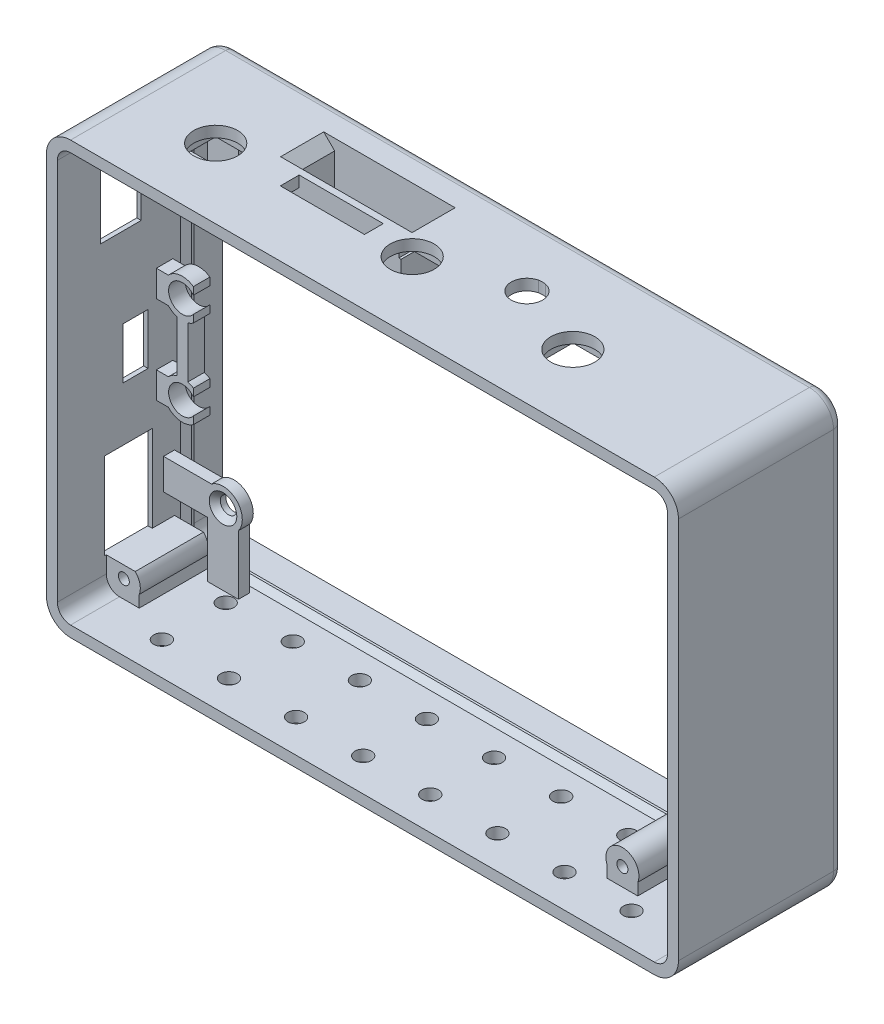
SolidWorks part; units mm, degrees
ref_plane "Спереди" through (0, 0, 0) normal (0, 0, 1) x (1, 0, 0)
ref_plane "Сверху" through (0, 0, 0) normal (0, 1, 0) x (1, 0, 0)
ref_plane "Справа" through (0, 0, 0) normal (1, 0, 0) x (0, 0, -1)
sketch "основной шаблон" plane through (0, 0, 0) normal (0, 0, 1) x (1, 0, 0)
  line L0 (57.46, -33.28) -> (57.46, 36.28)
  line L1 (53.06, 40.68) -> (-53.06, 40.68)
  line L2 (55.46, -33.28) -> (55.46, 36.28)
  line L3 (53.06, 38.68) -> (-53.06, 38.68)
  line L4 (53.357, 32.7) -> (55.46, 32.7)
  line L5 (49.48, 36.577) -> (49.48, 38.68)
  line L6 (35.5675, 36.5758) -> (35.5675, 38.68)
  line L7 (41.1675, 36.5758) -> (41.1675, 38.68)
  line L8 (-8.24, 37.68) -> (53.06, 37.68)
  line L9 (54.46, 36.28) -> (54.46, -33.28)
  line L10 (51.56, 22.97) -> (55.46, 22.97)
  line L11 (52.26, 28.57) -> (55.46, 28.57)
  line L12 (52.26, 28.57) -> (52.26, 32.5001)
  line L13 (46.66, 27.87) -> (46.66, 38.68)
  line L14 (-53.06, -35.68) -> (53.06, -35.68)
  line L15 (-53.06, -37.68) -> (53.06, -37.68)
  line L16 (41.1675, -33.5233) -> (41.1675, -35.68)
  line L17 (35.5675, -33.5233) -> (35.5675, -35.68)
  line L18 (49.48, -33.577) -> (49.48, -35.68)
  line L19 (53.357, -29.7) -> (55.46, -29.7)
  line L20 (53.06, -34.68) -> (-53.06, -34.68)
  line L21 (51.56, -19.97) -> (55.46, -19.97)
  line L22 (52.26, -25.57) -> (55.46, -25.57)
  line L23 (52.26, -25.57) -> (52.26, -29.5001)
  line L24 (46.66, -24.87) -> (46.66, -35.68)
  line L25 (50.06, -40.68) -> (46.06, -40.68)
  line L26 (46.06, -37.68) -> (46.06, -40.68)
  line L27 (50.06, -40.68) -> (50.06, -37.68)
  line L28 (-46.06, -40.68) -> (-50.06, -40.68)
  line L29 (-50.06, -37.68) -> (-50.06, -40.68)
  line L30 (-46.06, -40.68) -> (-46.06, -37.68)
  line L31 (-55.46, 36.28) -> (-55.46, -33.28)
  line L32 (-57.46, 36.28) -> (-57.46, -33.28)
  line L33 (-47.44, -25.57) -> (-47.44, -35.68)
  line L34 (-47.44, -25.57) -> (-55.46, -25.57)
  line L35 (-46.74, -19.97) -> (-55.46, -19.97)
  line L36 (-41.84, -24.87) -> (-41.84, -35.68)
  line L37 (-53.3558, -29.6462) -> (-55.46, -29.6462)
  line L38 (-55.46, -30.6537) -> (-49.8732, -30.6537)
  line L39 (-49.4788, -33.5233) -> (-49.4788, -35.68)
  line L40 (-54.46, -33.28) -> (-54.46, 36.28)
  line L41 (-53.2825, -5.7) -> (-55.3212, -5.7)
  line L42 (-48.735, -5.2277) -> (-48.735, -6.6)
  line L43 (-48.735, -9.6) -> (-48.735, -10.9723)
  line L44 (-55.46, -10.5) -> (-53.2825, -10.5)
  line L45 (-49.735, -4.7459) -> (-49.735, 4.5459)
  line L46 (-51.735, 4.5459) -> (-51.735, -4.7459)
  line L47 (-55.46, 5.5) -> (-53.2825, 5.5)
  line L48 (-53.2825, 10.3) -> (-55.46, 10.3)
  line L49 (-48.735, 10.7723) -> (-48.735, 9.4)
  line L50 (-48.735, 6.4) -> (-48.735, 5.0277)
  line L51 (-55.46, -30.28) -> (-56.66, -30.28)
  line L52 (-56.66, -31.8537) -> (-56.66, -13.3537)
  line L53 (-55.46, -14.5537) -> (-56.66, -14.5537)
  line L54 (-55.46, 4.5685) -> (-56.66, 4.5685)
  line L55 (-56.66, -5.9315) -> (-56.66, 5.7685)
  line L56 (-55.46, -4.7315) -> (-56.66, -4.7315)
  line L57 (-56.66, 12.5883) -> (-56.66, 33.9619)
  line L58 (-55.46, 13.7883) -> (-56.66, 13.7883)
  line L59 (-55.46, 32.7619) -> (-56.66, 32.7619)
  line L60 (-41.84, 27.87) -> (-41.84, 38.68)
  line L61 (-47.44, 28.57) -> (-47.44, 38.68)
  line L62 (-47.44, 28.57) -> (-55.46, 28.57)
  line L63 (-46.74, 22.97) -> (-55.46, 22.97)
  line L64 (-49.4785, 38.68) -> (-53.06, 38.68)
  line L65 (-53.06, 37.68) -> (-30.54, 37.68)
  line L66 (-49.4785, 36.576) -> (-49.4785, 38.68)
  line L67 (-51.0505, 32.7619) -> (-55.46, 32.7619)
  line L68 (8.897, 38.68) -> (15.497, 38.68)
  line L69 (15.497, 40.68) -> (8.897, 40.68)
  line L70 (-30.54, 29.68) -> (-30.54, 38.68)
  line L71 (-8.24, 29.68) -> (-30.54, 29.68)
  line L72 (-8.24, 29.68) -> (-8.24, 38.68)
  line L73 (-11.24, 30.88) -> (-11.24, 30.08)
  line L74 (-9.44, 30.08) -> (-9.44, 40.68)
  line L75 (-10.4737, 38.68) -> (-10.4737, 40.68)
  line L76 (-27.54, 29.68) -> (-27.54, 30.08)
  line L77 (-27.54, 30.88) -> (-27.54, 30.08)
  line L78 (-29.34, 30.08) -> (-29.34, 40.68)
  line L79 (-26.7737, 38.68) -> (-26.7737, 40.68)
  line L80 (-11.24, 29.68) -> (-11.24, 30.08)
  arc A0 (57.46, 36.28) -> (53.06, 40.68) centre (53.06, 36.28) ccw
  arc A1 (55.46, 36.28) -> (53.06, 38.68) centre (53.06, 36.28) ccw
  arc A2 (49.48, 36.577) -> (53.357, 32.7) centre (52.28, 35.5) ccw
  circle A3 centre (52.28, 35.5) radius 1
  circle A4 centre (38.3675, 35.4988) radius 1
  arc A5 (35.5675, 36.5758) -> (41.1675, 36.5758) centre (38.3675, 35.4988) ccw
  circle A6 centre (49.46, 25.77) radius 1.5
  arc A7 (46.66, 27.87) -> (51.56, 22.97) centre (49.46, 25.77) ccw
  arc A8 (54.46, 36.28) -> (53.06, 37.68) centre (53.06, 36.28) ccw
  arc A9 (53.06, -37.68) -> (57.46, -33.28) centre (53.06, -33.28) ccw
  arc A10 (53.06, -35.68) -> (55.46, -33.28) centre (53.06, -33.28) ccw
  circle A11 centre (38.3675, -32.4462) radius 1
  arc A12 (41.1675, -33.5233) -> (35.5675, -33.5233) centre (38.3675, -32.4462) ccw
  circle A13 centre (52.28, -32.5) radius 1
  arc A14 (53.357, -29.7) -> (49.48, -33.577) centre (52.28, -32.5) ccw
  circle A15 centre (49.46, -22.77) radius 1.5
  circle A16 centre (49.46, -22.77) radius 3.5
  arc A17 (53.06, -34.68) -> (54.46, -33.28) centre (53.06, -33.28) ccw
  arc A18 (-55.46, -33.28) -> (-53.06, -35.68) centre (-53.06, -33.28) ccw
  arc A19 (-57.46, -33.28) -> (-53.06, -37.68) centre (-53.06, -33.28) ccw
  circle A20 centre (-44.64, -22.77) radius 1.5
  circle A21 centre (-44.64, -22.77) radius 3.5
  arc A22 (-49.8732, -30.6537) -> (-53.3558, -29.6462) centre (-52.2788, -32.4462) ccw
  circle A23 centre (-52.2788, -32.4462) radius 1
  arc A24 (-49.4788, -33.5233) -> (-49.8732, -30.6537) centre (-52.2788, -32.4462) ccw
  arc A25 (-48.735, -5.2277) -> (-49.735, -4.7459) centre (-50.735, -8.1) ccw
  arc A26 (-51.735, -4.7459) -> (-53.2825, -5.7) centre (-50.735, -8.1) ccw
  arc A27 (-48.735, -6.6) -> (-48.735, -9.6) centre (-50.735, -8.1) ccw
  arc A28 (-53.2825, -10.5) -> (-48.735, -10.9723) centre (-50.735, -8.1) ccw
  arc A29 (-48.735, 9.4) -> (-48.735, 6.4) centre (-50.735, 7.9) ccw
  arc A30 (-49.735, 4.5459) -> (-48.735, 5.0277) centre (-50.735, 7.9) ccw
  arc A31 (-53.2825, 5.5) -> (-51.735, 4.5459) centre (-50.735, 7.9) ccw
  arc A32 (-48.735, 10.7723) -> (-53.2825, 10.3) centre (-50.735, 7.9) ccw
  arc A33 (-54.46, -33.28) -> (-53.06, -34.68) centre (-53.06, -33.28) ccw
  arc A34 (-56.66, -31.8537) -> (-57.46, -32.9851) centre (-56.26, -32.9851) ccw
  arc A35 (-57.46, -12.2223) -> (-56.66, -13.3537) centre (-56.26, -12.2223) ccw
  arc A36 (-57.46, 6.8999) -> (-56.66, 5.7685) centre (-56.26, 6.8999) ccw
  arc A37 (-56.66, -5.9315) -> (-57.46, -7.0629) centre (-56.26, -7.0629) ccw
  arc A38 (-56.66, 12.5883) -> (-57.46, 11.4569) centre (-56.26, 11.4569) ccw
  arc A39 (-57.46, 35.0932) -> (-56.66, 33.9619) centre (-56.26, 35.0932) ccw
  arc A40 (-53.06, 37.68) -> (-54.46, 36.28) centre (-53.06, 36.28) ccw
  arc A41 (-53.06, 40.68) -> (-57.46, 36.28) centre (-53.06, 36.28) ccw
  arc A42 (-53.06, 38.68) -> (-55.46, 36.28) centre (-53.06, 36.28) ccw
  circle A43 centre (-44.64, 25.77) radius 1.5
  circle A44 centre (-44.64, 25.77) radius 3.5
  circle A45 centre (-52.2785, 35.499) radius 1
  arc A46 (-53.3555, 32.699) -> (-51.0505, 32.7619) centre (-52.2785, 35.499) ccw
  arc A47 (-51.0505, 32.7619) -> (-49.4785, 36.576) centre (-52.2785, 35.499) ccw
sketch "Эскиз2" plane through (0, 0, 0) normal (0, 0, 1) x (1, 0, 0)
  line L0 (-55.46, 36.28) -> (-55.46, -33.28) construction
  line L1 (53.06, 38.68) -> (-53.06, 38.68) construction
  line L2 (-57.46, 36.28) -> (-57.46, -33.28) construction
  line L3 (53.06, 40.68) -> (-53.06, 40.68) construction
  line L4 (-55.46, 36.28) -> (-55.46, -33.28)
  line L5 (53.06, 38.68) -> (-53.06, 38.68)
  line L6 (-57.46, 36.28) -> (-57.46, -33.28)
  line L7 (53.06, 40.68) -> (-53.06, 40.68)
  line L8 (55.46, -33.28) -> (55.46, 36.28) construction
  line L9 (57.46, -33.28) -> (57.46, 36.28) construction
  line L10 (55.46, -33.28) -> (55.46, 36.28)
  line L11 (57.46, -33.28) -> (57.46, 36.28)
  line L12 (-53.06, -37.68) -> (53.06, -37.68) construction
  line L13 (-53.06, -35.68) -> (53.06, -35.68) construction
  line L14 (-53.06, -37.68) -> (53.06, -37.68)
  line L15 (-53.06, -35.68) -> (53.06, -35.68)
  arc A0 (-53.06, 38.68) -> (-55.46, 36.28) centre (-53.06, 36.28) ccw construction
  arc A1 (-53.06, 40.68) -> (-57.46, 36.28) centre (-53.06, 36.28) ccw construction
  arc A2 (-53.06, 38.68) -> (-55.46, 36.28) centre (-53.06, 36.28) ccw
  arc A3 (-53.06, 40.68) -> (-57.46, 36.28) centre (-53.06, 36.28) ccw
  arc A4 (57.46, 36.28) -> (53.06, 40.68) centre (53.06, 36.28) ccw construction
  arc A5 (55.46, 36.28) -> (53.06, 38.68) centre (53.06, 36.28) ccw construction
  arc A6 (57.46, 36.28) -> (53.06, 40.68) centre (53.06, 36.28) ccw
  arc A7 (55.46, 36.28) -> (53.06, 38.68) centre (53.06, 36.28) ccw
  arc A8 (53.06, -37.68) -> (57.46, -33.28) centre (53.06, -33.28) ccw construction
  arc A9 (53.06, -35.68) -> (55.46, -33.28) centre (53.06, -33.28) ccw construction
  arc A10 (53.06, -37.68) -> (57.46, -33.28) centre (53.06, -33.28) ccw
  arc A11 (53.06, -35.68) -> (55.46, -33.28) centre (53.06, -33.28) ccw
  arc A12 (-57.46, -33.28) -> (-53.06, -37.68) centre (-53.06, -33.28) ccw construction
  arc A13 (-55.46, -33.28) -> (-53.06, -35.68) centre (-53.06, -33.28) ccw construction
  arc A14 (-57.46, -33.28) -> (-53.06, -37.68) centre (-53.06, -33.28) ccw
  arc A15 (-55.46, -33.28) -> (-53.06, -35.68) centre (-53.06, -33.28) ccw
extrude "рамка" add sketch "Эскиз2" along normal blind 30
ref_plane "Плоскость4" through (0, 0, 6.2) normal (0, 0, -1) x (-1, 0, 0)
sketch "Эскиз6" plane through (0, 0, 6.2) normal (0, 0, -1) x (-1, 0, 0)
  line L0 (-55.46, -33.28) -> (-55.46, 36.28) construction
  line L1 (-54.46, 36.28) -> (-54.46, -33.28) construction
  line L2 (-55.46, -33.28) -> (-55.46, 36.28)
  line L3 (-54.46, 36.28) -> (-54.46, -33.28)
  line L4 (8.24, 37.68) -> (-53.06, 37.68) construction
  line L5 (8.24, 37.68) -> (-53.06, 37.68)
  line L6 (53.06, -35.68) -> (-53.06, -35.68) construction
  line L7 (-53.06, -34.68) -> (53.06, -34.68) construction
  line L8 (53.06, -35.68) -> (-53.06, -35.68)
  line L9 (-53.06, -34.68) -> (53.06, -34.68)
  line L10 (54.46, -33.28) -> (54.46, 36.28) construction
  line L11 (55.46, 36.28) -> (55.46, -33.28) construction
  line L12 (54.46, -33.28) -> (54.46, 36.28)
  line L13 (55.46, 36.28) -> (55.46, -33.28)
  line L14 (53.06, 37.68) -> (30.54, 37.68) construction
  line L15 (53.06, 37.68) -> (30.54, 37.68)
  line L16 (30.54, 37.68) -> (30.54, 38.68)
  line L17 (30.54, 38.68) -> (53.06, 38.68)
  line L18 (8.24, 37.68) -> (8.24, 38.68)
  line L19 (8.24, 38.68) -> (-53.06, 38.68)
  arc A0 (-53.06, 37.68) -> (-54.46, 36.28) centre (-53.06, 36.28) ccw construction
  arc A1 (-53.06, 38.68) -> (-55.46, 36.28) centre (-53.06, 36.28) ccw construction
  arc A2 (-53.06, 37.68) -> (-54.46, 36.28) centre (-53.06, 36.28) ccw
  arc A3 (-53.06, 38.68) -> (-55.46, 36.28) centre (-53.06, 36.28) ccw
  arc A4 (-55.46, -33.28) -> (-53.06, -35.68) centre (-53.06, -33.28) ccw construction
  arc A5 (-54.46, -33.28) -> (-53.06, -34.68) centre (-53.06, -33.28) ccw construction
  arc A6 (-55.46, -33.28) -> (-53.06, -35.68) centre (-53.06, -33.28) ccw
  arc A7 (-54.46, -33.28) -> (-53.06, -34.68) centre (-53.06, -33.28) ccw
  arc A8 (53.06, -34.68) -> (54.46, -33.28) centre (53.06, -33.28) ccw construction
  arc A9 (53.06, -35.68) -> (55.46, -33.28) centre (53.06, -33.28) ccw construction
  arc A10 (53.06, -34.68) -> (54.46, -33.28) centre (53.06, -33.28) ccw
  arc A11 (53.06, -35.68) -> (55.46, -33.28) centre (53.06, -33.28) ccw
  arc A12 (55.46, 36.28) -> (53.06, 38.68) centre (53.06, 36.28) ccw construction
  arc A13 (54.46, 36.28) -> (53.06, 37.68) centre (53.06, 36.28) ccw construction
  arc A14 (55.46, 36.28) -> (53.06, 38.68) centre (53.06, 36.28) ccw
  arc A15 (54.46, 36.28) -> (53.06, 37.68) centre (53.06, 36.28) ccw
extrude "юбка" add sketch "Эскиз6" against normal blind 2.4
chamfer "фаска юбки" distance 2 angle 45 9 edges at (-41.8, 37.68, 8.6) (-54.0499, 37.2699, 8.6) (-54.46, 1.5, 8.6) (-54.0499, -34.2699, 8.6) (0, -34.68, 8.6) (54.0499, -34.2699, 8.6) (54.46, 1.5, 8.6) (54.0499, 37.2699, 8.6) (22.41, 37.68, 8.6)
ref_plane "Плоскость5" through (0, 0, 8.7) normal (0, 0, -1) x (-1, 0, 0)
sketch "Эскиз7" plane through (0, 0, 8.7) normal (0, 0, -1) x (-1, 0, 0)
  line L0 (-35.5675, 36.5758) -> (-35.5675, 38.68) construction
  line L1 (-41.1675, 36.5758) -> (-41.1675, 38.68) construction
  line L2 (-35.5675, 36.5758) -> (-35.5675, 38.68)
  line L3 (-41.1675, 36.5758) -> (-41.1675, 38.68)
  line L4 (-41.1675, 38.68) -> (-35.5675, 38.68)
  line L5 (-49.48, 38.68) -> (-53.06, 38.68)
  line L6 (-53.357, 32.7) -> (-55.46, 32.7) construction
  line L7 (-52.26, 28.57) -> (-52.26, 32.5001) construction
  line L8 (-52.26, 28.57) -> (-55.46, 28.57) construction
  line L9 (-51.56, 22.97) -> (-55.46, 22.97) construction
  line L10 (-46.66, 27.87) -> (-46.66, 38.68) construction
  line L11 (-53.357, 32.7) -> (-55.46, 32.7)
  line L12 (-52.26, 28.57) -> (-52.26, 32.5001)
  line L13 (-52.26, 28.57) -> (-55.46, 28.57)
  line L14 (-51.56, 22.97) -> (-55.46, 22.97)
  line L15 (-46.66, 27.87) -> (-46.66, 38.68)
  line L16 (-46.66, 38.68) -> (-49.48, 38.68)
  line L17 (-55.46, 36.28) -> (-55.46, 32.7)
  line L18 (-55.46, 28.57) -> (-55.46, 22.97)
  line L19 (-41.1675, -33.5233) -> (-41.1675, -35.68) construction
  line L20 (-35.5675, -33.5233) -> (-35.5675, -35.68) construction
  line L21 (-41.1675, -33.5233) -> (-41.1675, -35.68)
  line L22 (-35.5675, -33.5233) -> (-35.5675, -35.68)
  line L23 (-52.26, -25.57) -> (-52.26, -29.5001) construction
  line L24 (-53.357, -29.7) -> (-55.46, -29.7) construction
  line L26 (-52.26, -25.57) -> (-55.46, -25.57) construction
  line L27 (-51.56, -19.97) -> (-55.46, -19.97) construction
  line L28 (-46.66, -24.87) -> (-46.66, -35.68) construction
  line L29 (-52.26, -25.57) -> (-52.26, -29.5001)
  line L30 (-53.357, -29.7) -> (-55.46, -29.7)
  line L32 (-52.26, -25.57) -> (-55.46, -25.57)
  line L33 (-51.56, -19.97) -> (-55.46, -19.97)
  line L34 (-46.66, -24.87) -> (-46.66, -35.68)
  line L35 (-55.46, -19.97) -> (-55.46, -25.57)
  line L37 (-55.46, -29.7) -> (-55.46, -33.28)
  line L38 (-53.06, -35.68) -> (-46.66, -35.68)
  line L39 (-35.5675, -35.68) -> (-41.1675, -35.68)
  line L40 (53.3558, -29.6462) -> (55.46, -29.6462) construction
  line L41 (49.4788, -33.5233) -> (49.4788, -35.68) construction
  line L42 (41.84, -24.87) -> (41.84, -35.68) construction
  line L43 (47.44, -25.57) -> (47.44, -35.68) construction
  line L44 (47.44, -25.57) -> (55.46, -25.57) construction
  line L45 (46.74, -19.97) -> (55.46, -19.97) construction
  line L46 (53.3558, -29.6462) -> (55.46, -29.6462)
  line L47 (49.4788, -33.5233) -> (49.4788, -35.68)
  line L48 (41.84, -24.87) -> (41.84, -35.68)
  line L49 (47.44, -25.57) -> (47.44, -35.68)
  line L50 (47.44, -25.57) -> (55.46, -25.57)
  line L51 (46.74, -19.97) -> (55.46, -19.97)
  line L52 (55.46, -19.97) -> (55.46, -25.57)
  line L53 (55.46, -29.6462) -> (55.46, -33.28)
  line L54 (53.06, -35.68) -> (49.4788, -35.68)
  line L55 (47.44, -35.68) -> (41.84, -35.68)
  line L56 (47.44, 28.57) -> (47.44, 38.68) construction
  line L57 (47.44, 28.57) -> (55.46, 28.57) construction
  line L58 (46.74, 22.97) -> (55.46, 22.97) construction
  line L59 (41.84, 27.87) -> (41.84, 38.68) construction
  line L60 (47.44, 28.57) -> (47.44, 38.68)
  line L61 (47.44, 28.57) -> (55.46, 28.57)
  line L62 (46.74, 22.97) -> (55.46, 22.97)
  line L63 (41.84, 27.87) -> (41.84, 38.68)
  line L64 (49.4785, 36.576) -> (49.4785, 38.68) construction
  line L65 (49.4785, 36.576) -> (49.4785, 38.68)
  line L66 (49.4785, 38.68) -> (53.06, 38.68)
  line L67 (41.84, 38.68) -> (47.44, 38.68)
  line L68 (55.46, 28.57) -> (55.46, 22.97)
  line L69 (53.3555, 32.699) -> (55.46, 32.699)
  line L70 (55.46, 32.699) -> (55.46, 36.28)
  circle A0 centre (-38.3675, 35.4988) radius 1 construction
  arc A1 (-41.1675, 36.5758) -> (-35.5675, 36.5758) centre (-38.3675, 35.4988) ccw construction
  circle A2 centre (-38.3675, 35.4988) radius 1
  arc A3 (-41.1675, 36.5758) -> (-35.5675, 36.5758) centre (-38.3675, 35.4988) ccw
  circle A4 centre (-52.28, 35.5) radius 1 construction
  arc A5 (-53.06, 38.68) -> (-55.46, 36.28) centre (-53.06, 36.28) ccw construction
  circle A6 centre (-49.46, 25.77) radius 1.5 construction
  arc A7 (-51.56, 22.97) -> (-46.66, 27.87) centre (-49.46, 25.77) ccw construction
  circle A8 centre (-52.28, 35.5) radius 1
  arc A9 (-53.06, 38.68) -> (-55.46, 36.28) centre (-53.06, 36.28) ccw
  circle A10 centre (-49.46, 25.77) radius 1.5
  arc A11 (-51.56, 22.97) -> (-46.66, 27.87) centre (-49.46, 25.77) ccw
  arc A12 (-53.357, 32.7) -> (-49.48, 36.577) centre (-52.28, 35.5) ccw construction
  arc A13 (-53.357, 32.7) -> (-49.48, 36.577) centre (-52.28, 35.5) ccw
  circle A14 centre (-38.3675, -32.4462) radius 1 construction
  arc A15 (-35.5675, -33.5233) -> (-41.1675, -33.5233) centre (-38.3675, -32.4462) ccw construction
  circle A16 centre (-38.3675, -32.4462) radius 1
  arc A17 (-35.5675, -33.5233) -> (-41.1675, -33.5233) centre (-38.3675, -32.4462) ccw
  circle A18 centre (-52.28, -32.5) radius 1 construction
  arc A19 (-49.48, -33.577) -> (-53.357, -29.7) centre (-52.28, -32.5) ccw construction
  circle A20 centre (-49.46, -22.77) radius 1.5 construction
  circle A21 centre (-52.28, -32.5) radius 1
  arc A22 (-52.26, -29.5001) -> (-53.357, -29.7) centre (-52.28, -32.5) ccw
  circle A23 centre (-49.46, -22.77) radius 1.5
  arc A24 (-55.46, -33.28) -> (-53.06, -35.68) centre (-53.06, -33.28) ccw construction
  arc A25 (-55.46, -33.28) -> (-53.06, -35.68) centre (-53.06, -33.28) ccw
  arc A26 (-51.56, -19.97) -> (-46.6624, -24.8732) centre (-49.46, -22.77) cw
  circle A27 centre (52.2788, -32.4462) radius 1 construction
  circle A28 centre (44.64, -22.77) radius 1.5 construction
  arc A29 (49.8732, -30.6537) -> (49.4788, -33.5233) centre (52.2788, -32.4462) ccw construction
  arc A30 (53.3558, -29.6462) -> (49.8732, -30.6537) centre (52.2788, -32.4462) ccw construction
  circle A31 centre (52.2788, -32.4462) radius 1
  circle A32 centre (44.64, -22.77) radius 1.5
  arc A33 (49.8732, -30.6537) -> (49.4788, -33.5233) centre (52.2788, -32.4462) ccw
  arc A34 (53.3558, -29.6462) -> (49.8732, -30.6537) centre (52.2788, -32.4462) ccw
  arc A35 (53.06, -35.68) -> (55.46, -33.28) centre (53.06, -33.28) ccw construction
  arc A36 (53.06, -35.68) -> (55.46, -33.28) centre (53.06, -33.28) ccw
  arc A37 (41.84, -24.87) -> (46.74, -19.97) centre (44.64, -22.77) cw
  circle A38 centre (44.64, 25.77) radius 1.5 construction
  circle A39 centre (44.64, 25.77) radius 1.5
  arc A40 (51.0505, 32.7619) -> (53.3555, 32.699) centre (52.2785, 35.499) ccw construction
  arc A41 (55.46, 36.28) -> (53.06, 38.68) centre (53.06, 36.28) ccw construction
  arc A42 (49.4785, 36.576) -> (51.0505, 32.7619) centre (52.2785, 35.499) ccw construction
  circle A43 centre (52.2785, 35.499) radius 1 construction
  arc A44 (51.0505, 32.7619) -> (53.3555, 32.699) centre (52.2785, 35.499) ccw
  arc A45 (55.46, 36.28) -> (53.06, 38.68) centre (53.06, 36.28) ccw
  arc A46 (49.4785, 36.576) -> (51.0505, 32.7619) centre (52.2785, 35.499) ccw
  circle A47 centre (52.2785, 35.499) radius 1
  arc A48 (46.74, 22.97) -> (41.84, 27.87) centre (44.64, 25.77) cw
extrude "крепежи" add sketch "Эскиз7" against normal blind 2 contours L3 A3 L2 L4 A2 | L11 A13 L12 L13 L18 L14 A11 L15 L16 L5 A9 L17 A8 A10 | A26 L33 L35 L32 L29 A22 L30 L37 A25 L38 L34 A23 A21 | L22 A17 L21 L39 A16 | A37 L48 L55 L49 L50 L52 L51 A32 | L54 A36 L53 L46 A34 A33 L47 A31 | A48 L62 L68 L61 L60 L67 L63 A39 | L65 A46 A44 L69 L70 A45 L66 A47 region at (38.3675, 32.5849, 8.7) region at (50.6709, 30.7403, 8.7) region at (38.3675, -29.5328, 8.7) region at (50.6709, -27.7403, 8.7) region at (-54.4079, -29.734, 8.7) region at (-46.9567, -26.1582, 8.7) region at (-46.9567, 29.1582, 8.7) region at (-49.5659, 37.628, 8.7)
sketch "Эскиз8" plane through (0, 0, 10.7) normal (0, 0, 1) x (1, 0, 0)
  line L3 (41.1675, 36.5758) -> (41.1675, 38.68)
  line L4 (-49.4785, 36.576) -> (-49.4785, 38.68)
  line L5 (-49.4785, 38.68) -> (-53.06, 38.68)
  line L6 (-55.46, 36.28) -> (-55.46, 32.699)
  line L7 (-55.46, 32.699) -> (-53.3555, 32.699)
  line L8 (-49.4785, 36.576) -> (-49.4785, 38.68)
  line L9 (-49.4785, 38.68) -> (-53.06, 38.68)
  line L10 (-55.46, 36.28) -> (-55.46, 32.699)
  line L11 (-55.46, 32.699) -> (-53.3555, 32.699)
  line L12 (41.1675, 38.68) -> (35.5675, 38.68)
  line L13 (35.5675, 38.68) -> (35.5675, 36.5758)
  line L14 (41.1675, 36.5758) -> (41.1675, 38.68)
  line L15 (41.1675, 38.68) -> (35.5675, 38.68)
  line L16 (35.5675, 38.68) -> (35.5675, 36.5758)
  line L17 (35.5675, -33.5233) -> (35.5675, -35.68)
  line L18 (35.5675, -35.68) -> (41.1675, -35.68)
  line L19 (41.1675, -35.68) -> (41.1675, -33.5233)
  line L20 (35.5675, -33.5233) -> (35.5675, -35.68)
  line L21 (35.5675, -35.68) -> (41.1675, -35.68)
  line L22 (41.1675, -35.68) -> (41.1675, -33.5233)
  line L24 (-53.06, -35.68) -> (-49.4788, -35.68)
  line L25 (-49.4788, -35.68) -> (-49.4788, -33.5233)
  line L26 (-53.3558, -29.6462) -> (-55.46, -29.6462)
  line L27 (-55.46, -29.6462) -> (-55.46, -33.28)
  line L28 (-53.06, -35.68) -> (-49.4788, -35.68)
  line L29 (-49.4788, -35.68) -> (-49.4788, -33.5233)
  line L30 (-53.3558, -29.6462) -> (-55.46, -29.6462)
  line L31 (-55.46, -29.6462) -> (-55.46, -33.28)
  circle A0 centre (38.3675, 35.4988) radius 1 construction
  circle A1 centre (-52.2785, 35.499) radius 1 construction
  arc A2 (-53.06, 38.68) -> (-55.46, 36.28) centre (-53.06, 36.28) ccw
  arc A3 (-53.3555, 32.699) -> (-49.4785, 36.576) centre (-52.2785, 35.499) ccw
  arc A4 (-53.06, 38.68) -> (-55.46, 36.28) centre (-53.06, 36.28) ccw
  arc A5 (-53.3555, 32.699) -> (-49.4785, 36.576) centre (-52.2785, 35.499) ccw
  circle A6 centre (38.3675, 35.4988) radius 1
  circle A7 centre (-52.2785, 35.499) radius 1
  circle A8 centre (38.3675, -32.4462) radius 1 construction
  arc A9 (35.5675, 36.5758) -> (41.1675, 36.5758) centre (38.3675, 35.4988) ccw
  arc A10 (35.5675, 36.5758) -> (41.1675, 36.5758) centre (38.3675, 35.4988) ccw
  arc A11 (41.1675, -33.5233) -> (35.5675, -33.5233) centre (38.3675, -32.4462) ccw
  arc A12 (41.1675, -33.5233) -> (35.5675, -33.5233) centre (38.3675, -32.4462) ccw
  circle A13 centre (38.3675, -32.4462) radius 1
  circle A14 centre (-52.2788, -32.4462) radius 1 construction
  circle A15 centre (-52.2788, -32.4462) radius 1
  arc A16 (-49.4788, -33.5233) -> (-53.3558, -29.6462) centre (-52.2788, -32.4462) ccw
  arc A17 (-55.46, -33.28) -> (-53.06, -35.68) centre (-53.06, -33.28) ccw
  arc A18 (-49.4788, -33.5233) -> (-53.3558, -29.6462) centre (-52.2788, -32.4462) ccw
  arc A19 (-55.46, -33.28) -> (-53.06, -35.68) centre (-53.06, -33.28) ccw
  dimension "D1" = 0
  dimension "D2" = 0
  dimension "D3" = 0
  dimension "D4" = 0
extrude "крепеж платы" add sketch "Эскиз8" along normal blind 10.4
sketch "Эскиз9" plane through (0, 0, 10.7) normal (0, 0, 1) x (1, 0, 0)
  line L0 (53.357, 32.7) -> (55.46, 32.7) construction
  line L1 (49.48, 36.577) -> (49.48, 38.68) construction
  line L2 (53.357, 32.7) -> (55.46, 32.7)
  line L3 (49.48, 36.577) -> (49.48, 38.68)
  line L4 (53.06, 38.68) -> (49.48, 38.68)
  line L5 (55.46, 36.28) -> (55.46, 32.7)
  line L6 (49.48, -33.577) -> (49.48, -35.68) construction
  line L7 (53.357, -29.7) -> (55.46, -29.7) construction
  line L8 (49.48, -33.577) -> (49.48, -35.68)
  line L9 (53.357, -29.7) -> (55.46, -29.7)
  line L10 (55.46, -29.7) -> (55.46, -33.28)
  line L11 (53.06, -35.68) -> (49.48, -35.68)
  arc A0 (55.46, 36.28) -> (53.06, 38.68) centre (53.06, 36.28) ccw construction
  circle A1 centre (52.28, 35.5) radius 1 construction
  arc A2 (49.48, 36.577) -> (53.357, 32.7) centre (52.28, 35.5) ccw construction
  arc A3 (55.46, 36.28) -> (53.06, 38.68) centre (53.06, 36.28) ccw
  circle A4 centre (52.28, 35.5) radius 1
  arc A5 (49.48, 36.577) -> (53.357, 32.7) centre (52.28, 35.5) ccw
  arc A6 (53.357, -29.7) -> (49.48, -33.577) centre (52.28, -32.5) ccw construction
  arc A7 (53.06, -35.68) -> (55.46, -33.28) centre (53.06, -33.28) ccw construction
  circle A8 centre (52.28, -32.5) radius 1 construction
  arc A9 (53.357, -29.7) -> (49.48, -33.577) centre (52.28, -32.5) ccw
  arc A10 (53.06, -35.68) -> (55.46, -33.28) centre (53.06, -33.28) ccw
  circle A11 centre (52.28, -32.5) radius 1
extrude "крепеж крышки" add sketch "Эскиз9" along normal blind 12.4
ref_plane "Плоскость6" through (0, 0, 12) normal (0, 0, -1) x (-1, 0, 0)
sketch "Эскиз11" plane through (0, 0, 12) normal (0, 0, -1) x (-1, 0, 0)
  line L0 (55.46, 5.5) -> (53.2825, 5.5) construction
  line L1 (51.735, 4.5459) -> (51.735, -4.7459) construction
  line L2 (49.735, -4.7459) -> (49.735, 4.5459) construction
  line L3 (48.735, 6.4) -> (48.735, 5.0277) construction
  line L4 (48.735, 10.7723) -> (48.735, 9.4) construction
  line L5 (53.2825, 10.3) -> (55.46, 10.3) construction
  line L6 (55.46, 5.5) -> (53.2825, 5.5)
  line L7 (51.735, 4.5459) -> (51.735, -4.7459)
  line L8 (49.735, -4.7459) -> (49.735, 4.5459)
  line L9 (48.735, 6.4) -> (48.735, 5.0277)
  line L10 (48.735, 10.7723) -> (48.735, 9.4)
  line L11 (53.2825, 10.3) -> (55.46, 10.3)
  line L12 (55.46, -10.5) -> (53.2825, -10.5) construction
  line L13 (48.735, -9.6) -> (48.735, -10.9723) construction
  line L14 (48.735, -5.2277) -> (48.735, -6.6) construction
  line L15 (53.2825, -5.7) -> (55.3212, -5.7) construction
  line L16 (55.46, -10.5) -> (53.2825, -10.5)
  line L17 (48.735, -9.6) -> (48.735, -10.9723)
  line L18 (48.735, -5.2277) -> (48.735, -6.6)
  line L19 (53.2825, -5.7) -> (55.3212, -5.7)
  line L20 (55.46, -10.5) -> (55.46, -5.7)
  line L21 (55.46, 36.28) -> (55.46, -33.28) construction
  line L22 (55.46, -5.7) -> (55.3212, -5.7)
  line L23 (55.46, 10.3) -> (55.46, 5.5)
  arc A0 (51.735, 4.5459) -> (53.2825, 5.5) centre (50.735, 7.9) ccw construction
  arc A1 (48.735, 5.0277) -> (49.735, 4.5459) centre (50.735, 7.9) ccw construction
  arc A2 (48.735, 6.4) -> (48.735, 9.4) centre (50.735, 7.9) ccw construction
  arc A3 (53.2825, 10.3) -> (48.735, 10.7723) centre (50.735, 7.9) ccw construction
  arc A4 (51.735, 4.5459) -> (53.2825, 5.5) centre (50.735, 7.9) ccw
  arc A5 (48.735, 5.0277) -> (49.735, 4.5459) centre (50.735, 7.9) ccw
  arc A6 (48.735, 6.4) -> (48.735, 9.4) centre (50.735, 7.9) ccw
  arc A7 (53.2825, 10.3) -> (48.735, 10.7723) centre (50.735, 7.9) ccw
  arc A8 (48.735, -10.9723) -> (53.2825, -10.5) centre (50.735, -8.1) ccw construction
  arc A9 (48.735, -9.6) -> (48.735, -6.6) centre (50.735, -8.1) ccw construction
  arc A10 (49.735, -4.7459) -> (48.735, -5.2277) centre (50.735, -8.1) ccw construction
  arc A11 (53.2825, -5.7) -> (51.735, -4.7459) centre (50.735, -8.1) ccw construction
  arc A12 (48.735, -10.9723) -> (53.2825, -10.5) centre (50.735, -8.1) ccw
  arc A13 (48.735, -9.6) -> (48.735, -6.6) centre (50.735, -8.1) ccw
  arc A14 (49.735, -4.7459) -> (48.735, -5.2277) centre (50.735, -8.1) ccw
  arc A15 (53.2825, -5.7) -> (51.735, -4.7459) centre (50.735, -8.1) ccw
extrude "поддержка кнопок" add sketch "Эскиз11" along normal blind 3
sketch "Эскиз13" plane through (0, -37.68, 0) normal (0, -1, 0) x (1, 0, 0)
  line L0 (-53.06, 30) -> (53.06, 30) construction
  line L1 (-57.46, 30) -> (-57.46, 0) construction
  circle A0 centre (-42.46, 24) radius 1.5
  circle A1 centre (-30.26, 24) radius 1.5
  circle A2 centre (-18.06, 24) radius 1.5
  circle A3 centre (-5.86, 24) radius 1.5
  circle A4 centre (6.34, 24) radius 1.5
  circle A5 centre (18.54, 24) radius 1.5
  circle A6 centre (30.74, 24) radius 1.5
  circle A7 centre (-30.26, 12.4) radius 1.5
  circle A8 centre (-18.06, 12.4) radius 1.5
  circle A9 centre (-5.86, 12.4) radius 1.5
  circle A10 centre (6.34, 12.4) radius 1.5
  circle A11 centre (18.54, 12.4) radius 1.5
  circle A12 centre (30.74, 12.4) radius 1.5
  circle A13 centre (-42.46, 12.4) radius 1.5
  circle A14 centre (42.94, 24) radius 1.5
  circle A15 centre (42.94, 12.4) radius 1.5
  dimension "D1" = 3
  dimension "D2" = 6
  dimension "D3" = 15
  dimension "D4" = 8
  dimension "D5" = 2
extrude "вентиляция" cut sketch "Эскиз13" against normal blind 2
sketch "Эскиз15" plane through (0, -37.68, 0) normal (0, -1, 0) x (1, 0, 0)
  line L0 (-50.06, 0) -> (-50.06, 35.1753) construction
  line L1 (-46.06, 0) -> (-46.06, 35.1753) construction
  line L2 (46.06, 0) -> (46.06, 33.4905) construction
  line L3 (50.06, 0) -> (50.06, 33.4905) construction
  line L4 (-53.06, 30) -> (53.06, 30) construction
  line L5 (-50.06, 2) -> (-46.06, 2)
  line L6 (-50.06, 2) -> (-50.06, 30)
  line L7 (-50.06, 30) -> (-46.06, 30)
  line L8 (-46.06, 2) -> (-46.06, 30)
  line L9 (-53.06, 0) -> (53.06, 0) construction
  line L10 (46.06, 2) -> (50.06, 2)
  line L11 (46.06, 2) -> (46.06, 30)
  line L12 (46.06, 30) -> (50.06, 30)
  line L13 (50.06, 2) -> (50.06, 30)
  dimension "D1" = 2
  dimension "D2" = 2
extrude "ножки" add sketch "Эскиз15" along normal blind 3
chamfer "фаска ножек" distance 3 angle 45 4 edges at (-48.06, -40.68, 30) (-48.06, -40.68, 2) (48.06, -40.68, 2) (48.06, -40.68, 30)
fillet "скругление лица" radius 1.8 8 edges at (56.1713, -36.3913, 0) (0, -37.68, 0) (-56.1713, -36.3913, 0) (-57.46, 1.5, 0) (-56.1713, 39.3913, 0) (0, 40.68, 0) (56.1713, 39.3913, 0) (57.46, 1.5, 0)
sketch "боковой шаблон" plane through (-57.46, 0, 0) normal (-1, 0, 0) x (0, 0, 1)
  line L0 (29.9989, 40.6801) -> (1.9989, 40.6801)
  line L1 (-0.0011, -33.2799) -> (-0.0011, 36.2801)
  line L2 (29.9989, 36.2801) -> (29.9989, -33.2799)
  line L3 (13.5569, 12.5884) -> (23.3989, 12.5884)
  line L4 (13.5569, 33.962) -> (13.5569, 12.5884)
  line L5 (23.3989, 12.5884) -> (23.3989, 33.962)
  line L6 (23.3989, 33.962) -> (13.5569, 33.962)
  line L7 (22.1989, 13.7884) -> (14.7569, 13.7884)
  line L8 (14.7569, 13.7884) -> (14.7569, 32.6991)
  line L9 (22.1989, 32.762) -> (22.1989, 13.7884)
  line L10 (14.7569, 32.6991) -> (22.1989, 32.762)
  line L11 (19.2989, -5.9314) -> (19.2989, 5.7686)
  line L12 (19.2989, 5.7686) -> (12.2989, 5.7686)
  line L13 (13.4989, -4.7314) -> (13.4989, 4.5686)
  line L14 (13.4989, 4.5686) -> (18.0989, 4.5686)
  line L15 (18.0989, 4.5686) -> (18.0989, -4.7314)
  line L16 (18.0989, -4.7314) -> (13.4989, -4.7314)
  line L17 (12.2989, -5.9314) -> (19.2989, -5.9314)
  line L18 (12.2989, 5.7686) -> (12.2989, -5.9314)
  line L19 (22.6689, -13.3536) -> (11.5489, -13.3536)
  line L20 (12.7489, -14.5536) -> (21.4689, -14.5536)
  line L21 (21.4689, -14.5536) -> (21.4689, -30.2799)
  line L22 (22.6689, -31.8536) -> (22.6689, -13.3536)
  line L23 (21.4689, -30.2799) -> (12.7489, -30.2799)
  line L24 (11.5489, -31.8536) -> (22.6689, -31.8536)
  line L25 (12.7489, -30.2799) -> (12.7489, -14.5536)
  line L26 (11.5489, -13.3536) -> (11.5489, -31.8536)
  line L27 (29.9989, -37.6799) -> (29.9989, -33.2799)
  line L28 (29.5989, -37.6799) -> (2.3989, -37.6799)
  line L29 (-0.0011, 38.8801) -> (-0.0011, 36.2801)
  line L30 (29.9989, 36.2801) -> (29.9989, 40.6801)
  line L31 (-0.0011, -33.2799) -> (-0.0011, -35.8799)
  arc A0 (1.7989, 40.6801) -> (-0.0011, 38.8801) centre (1.7989, 38.8801) ccw
  arc A1 (-0.0011, -35.8799) -> (1.7989, -37.6799) centre (1.7989, -35.8799) ccw
sketch "Эскиз17" plane through (-57.46, 0, 0) normal (-1, 0, 0) x (0, 0, 1)
  line L0 (18.0989, -4.7314) -> (13.4989, -4.7314) construction
  line L1 (13.4989, -4.7314) -> (13.4989, 4.5686) construction
  line L2 (13.4989, 4.5686) -> (18.0989, 4.5686) construction
  line L3 (18.0989, 4.5686) -> (18.0989, -4.7314) construction
  line L4 (22.1989, 13.7884) -> (14.7569, 13.7884) construction
  line L5 (14.7569, 13.7884) -> (14.7569, 32.6991) construction
  line L6 (14.7569, 32.6991) -> (22.1989, 32.762) construction
  line L7 (22.1989, 32.762) -> (22.1989, 13.7884) construction
  line L8 (18.0989, -4.7314) -> (13.4989, -4.7314)
  line L9 (13.4989, -4.7314) -> (13.4989, 4.5686)
  line L10 (13.4989, 4.5686) -> (18.0989, 4.5686)
  line L11 (18.0989, 4.5686) -> (18.0989, -4.7314)
  line L12 (22.1989, 13.7884) -> (14.7569, 13.7884)
  line L13 (14.7569, 13.7884) -> (14.7569, 32.6991)
  line L14 (14.7569, 32.6991) -> (22.1989, 32.762)
  line L15 (22.1989, 32.762) -> (22.1989, 13.7884)
  line L16 (21.4689, -14.5536) -> (21.4689, -30.2799) construction
  line L17 (21.4689, -30.2799) -> (12.7489, -30.2799) construction
  line L18 (12.7489, -30.2799) -> (12.7489, -14.5536) construction
  line L19 (12.7489, -14.5536) -> (21.4689, -14.5536) construction
  line L20 (21.4689, -14.5536) -> (21.4689, -30.2799)
  line L21 (21.4689, -30.2799) -> (12.7489, -30.2799)
  line L22 (12.7489, -30.2799) -> (12.7489, -14.5536)
  line L23 (12.7489, -14.5536) -> (21.4689, -14.5536)
extrude "боковые отверстия" cut sketch "Эскиз17" against normal blind 12
sketch "Эскиз18" plane through (-57.46, 0, 0) normal (-1, 0, 0) x (0, 0, 1)
  line L0 (19.2989, -5.9314) -> (19.2989, 5.7686) construction
  line L1 (19.2989, 5.7686) -> (12.2989, 5.7686) construction
  line L2 (13.5569, 12.5884) -> (23.3989, 12.5884) construction
  line L3 (13.5569, 33.962) -> (13.5569, 12.5884) construction
  line L4 (23.3989, 33.962) -> (13.5569, 33.962) construction
  line L5 (23.3989, 12.5884) -> (23.3989, 33.962) construction
  line L6 (19.2989, -5.9314) -> (19.2989, 5.7686)
  line L7 (19.2989, 5.7686) -> (12.2989, 5.7686)
  line L8 (13.5569, 12.5884) -> (23.3989, 12.5884)
  line L9 (13.5569, 33.962) -> (13.5569, 12.5884)
  line L10 (23.3989, 33.962) -> (13.5569, 33.962)
  line L11 (23.3989, 12.5884) -> (23.3989, 33.962)
  line L12 (11.5489, -31.8536) -> (22.6689, -31.8536) construction
  line L13 (11.5489, -13.3536) -> (11.5489, -31.8536) construction
  line L14 (22.6689, -31.8536) -> (22.6689, -13.3536) construction
  line L15 (22.6689, -13.3536) -> (11.5489, -13.3536) construction
  line L16 (12.2989, -5.9314) -> (19.2989, -5.9314) construction
  line L17 (12.2989, 5.7686) -> (12.2989, -5.9314) construction
  line L18 (11.5489, -31.8536) -> (22.6689, -31.8536)
  line L19 (11.5489, -13.3536) -> (11.5489, -31.8536)
  line L20 (22.6689, -31.8536) -> (22.6689, -13.3536)
  line L21 (22.6689, -13.3536) -> (11.5489, -13.3536)
  line L22 (12.2989, -5.9314) -> (19.2989, -5.9314)
  line L23 (12.2989, 5.7686) -> (12.2989, -5.9314)
extrude "углубление у боковых отверстий" cut sketch "Эскиз18" against normal blind 1.2
fillet "фаска боковых отверстий" radius 1.2 12 edges at (-57.46, 23.2752, 23.3989) (-57.46, 33.962, 18.4779) (-57.46, -31.8536, 17.1089) (-57.46, -22.6036, 22.6689) (-57.46, -22.6036, 11.5489) (-57.46, -13.3536, 17.1089) (-57.46, -5.9314, 15.7989) (-57.46, -0.0814, 19.2989) (-57.46, 5.7686, 15.7989) (-57.46, -0.0814, 12.2989) (-57.46, 23.2752, 13.5569) (-57.46, 12.5884, 18.4779)
sketch "верхний шаблон" plane through (0, 40.68, 0) normal (0, 1, 0) x (1, 0, 0)
  line L0 (57.46, -30) -> (57.46, 0)
  line L1 (55.66, 0) -> (53.06, 0)
  line L2 (-53.06, 0) -> (53.06, 0)
  line L3 (-29.34, -13.53) -> (-9.44, -13.53)
  line L4 (-29.34, -13.53) -> (-29.34, -5.7)
  line L5 (-11.24, -7.5) -> (-27.54, -7.5)
  line L6 (-27.54, -7.5) -> (-27.54, -10.95)
  line L7 (-29.34, -5.7) -> (-9.44, -5.7)
  line L8 (-27.54, -10.95) -> (-11.24, -10.95)
  line L9 (-9.44, -13.53) -> (-9.44, -5.7)
  line L10 (-11.24, -10.95) -> (-11.24, -7.5)
  line L11 (-26.7737, -14.73) -> (-26.7737, -18.15)
  line L12 (-26.7737, -18.15) -> (-10.4737, -18.15)
  line L13 (-10.4737, -14.73) -> (-26.7737, -14.73)
  line L14 (-10.4737, -18.15) -> (-10.4737, -14.73)
  line L15 (-53.06, 0) -> (-55.66, 0)
  line L16 (53.06, -30) -> (-53.06, -30)
  line L17 (-57.46, -30) -> (-57.46, 0)
  arc A0 (57.46, -1.8) -> (55.66, 0) centre (55.66, -1.8) ccw
  arc A1 (-1.9012, -17.3) -> (-5.4012, -17.3) centre (-3.6512, -17.3) ccw
  arc A2 (-5.4012, -17.3) -> (-1.9012, -17.3) centre (-3.6512, -17.3) ccw
  circle A3 centre (12.197, -12.7479) radius 3.3
  arc A4 (27.3088, -17.3) -> (23.8088, -17.3) centre (25.5588, -17.3) ccw
  arc A5 (23.8088, -17.3) -> (27.3088, -17.3) centre (25.5588, -17.3) ccw
  arc A6 (-55.66, 0) -> (-57.46, -1.8) centre (-55.66, -1.8) ccw
  arc A7 (-37.62, -17.3) -> (-41.12, -17.3) centre (-39.37, -17.3) ccw
  arc A8 (-41.12, -17.3) -> (-37.62, -17.3) centre (-39.37, -17.3) ccw
sketch "Эскиз20" plane through (0, 40.68, 0) normal (0, 1, 0) x (1, 0, 0)
  line L0 (-29.34, -5.7) -> (-9.44, -5.7) construction
  line L1 (-9.44, -13.53) -> (-9.44, -5.7) construction
  line L2 (-29.34, -5.7) -> (-9.44, -5.7)
  line L3 (-9.44, -13.53) -> (-9.44, -5.7)
  line L4 (-10.4737, -14.73) -> (-26.7737, -14.73) construction
  line L5 (-26.7737, -14.73) -> (-26.7737, -18.15) construction
  line L6 (-29.34, -13.53) -> (-9.44, -13.53) construction
  line L7 (-29.34, -13.53) -> (-29.34, -5.7) construction
  line L8 (-10.4737, -14.73) -> (-26.7737, -14.73)
  line L9 (-26.7737, -14.73) -> (-26.7737, -18.15)
  line L10 (-29.34, -13.53) -> (-9.44, -13.53)
  line L11 (-29.34, -13.53) -> (-29.34, -5.7)
  line L12 (-10.4737, -18.15) -> (-10.4737, -14.73) construction
  line L13 (-26.7737, -18.15) -> (-10.4737, -18.15) construction
  line L14 (-10.4737, -18.15) -> (-10.4737, -14.73)
  line L15 (-26.7737, -18.15) -> (-10.4737, -18.15)
  circle A0 centre (12.197, -12.7479) radius 3.3 construction
  circle A1 centre (12.197, -12.7479) radius 3.3
extrude "верхние отверстия" cut sketch "Эскиз20" against normal blind 2
sketch "Эскиз23" plane through (0, 38.68, 0) normal (0, -1, 0) x (1, 0, 0)
  line L0 (-9.44, 5.7) -> (-29.34, 5.7) construction
  line L1 (-29.34, 5.7) -> (-29.34, 13.53) construction
  line L2 (-29.34, 13.53) -> (-9.44, 13.53) construction
  line L3 (-9.44, 13.53) -> (-9.44, 5.7) construction
  line L4 (-9.44, 5.7) -> (-29.34, 5.7)
  line L5 (-29.34, 5.7) -> (-29.34, 13.53)
  line L6 (-29.34, 13.53) -> (-9.44, 13.53)
  line L7 (-9.44, 13.53) -> (-9.44, 5.7)
extrude "карман microsd" add sketch "Эскиз23" along normal blind 9 thin thin type one direction wall 1.2
sketch "Эскиз24" plane through (0, 29.68, 0) normal (0, -1, 0) x (1, 0, 0)
  line L4 (-8.24, 4.5) -> (-8.24, 14.73)
  line L5 (-8.24, 14.73) -> (-30.54, 14.73)
  line L6 (-30.54, 14.73) -> (-30.54, 4.5)
  line L7 (-30.54, 4.5) -> (-8.24, 4.5)
  line L8 (-8.24, 4.5) -> (-8.24, 14.73)
  line L9 (-8.24, 14.73) -> (-30.54, 14.73)
  line L10 (-30.54, 14.73) -> (-30.54, 4.5)
  line L11 (-30.54, 4.5) -> (-8.24, 4.5)
  dimension "D1" = 0
extrude "дно кармана microsd" add sketch "Эскиз24" against normal blind 1.2
sketch "Эскиз25" plane through (0, 30.88, 0) normal (0, 1, 0) x (1, 0, 0)
  line L0 (-27.54, -7.5) -> (-27.54, -10.95) construction
  line L1 (-27.54, -10.95) -> (-11.24, -10.95) construction
  line L2 (-11.24, -10.95) -> (-11.24, -7.5) construction
  line L3 (-11.24, -7.5) -> (-27.54, -7.5) construction
  line L4 (-27.54, -7.5) -> (-27.54, -10.95)
  line L5 (-27.54, -10.95) -> (-11.24, -10.95)
  line L6 (-11.24, -10.95) -> (-11.24, -7.5)
  line L7 (-11.24, -7.5) -> (-27.54, -7.5)
extrude "отверстие кармана microsd" cut sketch "Эскиз25" against normal blind 1.2
chamfer "Фаска8" distance 1 angle 45 4 edges at (47.96, 25.77, 10.7) (47.96, -22.77, 10.7) (-46.14, -22.77, 10.7) (-46.14, 25.77, 10.7)
chamfer "Фаска9" distance 2 angle 45 2 edges at (-8.24, 38.68, 9.615)
chamfer "Фаска10" distance 2 angle 45 2 edges at (-29.34, 40.68, 9.615) (-9.44, 40.68, 9.615)
sketch "Эскиз26" plane through (0, 40.68, 0) normal (0, 1, 0) x (1, 0, 0)
  line L0 (-26.7737, -18.15) -> (-10.4737, -18.15) construction
  line L1 (-10.4737, -14.73) -> (-11.4737, -14.73)
  line L2 (-10.4737, -14.73) -> (-10.4737, -18.15)
  line L3 (-10.4737, -18.15) -> (-11.4737, -18.15)
  line L4 (-11.4737, -14.73) -> (-11.4737, -18.15)
  dimension "D1" = 1
extrude "Бобышка-Вытянуть1" add sketch "Эскиз26" against normal blind 2
sketch "Эскиз27" plane through (0, 40.68, 0) normal (0, 1, 0) x (1, 0, 0)
  circle A0 centre (12.197, -12.2879) radius 2.85
  circle A1 centre (12.197, -12.7479) radius 3.3 construction
  dimension "D2" = 5.7
  dimension "D1" = 0.46
extrude "Вытянуть-Тонкостенный1" add sketch "Эскиз27" against normal blind 2 thin thin type one direction wall 1
sketch "Эскиз28" plane through (0, 0, 12.7489) normal (0, 0, 1) x (1, 0, 0)
  line L0 (-55.46, -29.6462) -> (-53.3558, -29.6462) construction
  line L1 (-55.46, -29.6462) -> (-53.3558, -29.6462)
  line L2 (-50.2035, -30.2799) -> (-55.46, -30.2799)
  line L3 (-50.2035, -30.2799) -> (-56.26, -30.2799) construction
  line L4 (-55.46, -30.2799) -> (-55.46, -29.6462)
  line L5 (-51.2011, 32.6991) -> (-53.3555, 32.699)
  arc A0 (-50.2035, -30.2799) -> (-53.3558, -29.6462) centre (-52.2788, -32.4462) ccw construction
  arc A1 (-50.2035, -30.2799) -> (-53.3558, -29.6462) centre (-52.2788, -32.4462) ccw
  arc A2 (-53.3555, 32.699) -> (-51.2011, 32.6991) centre (-52.2785, 35.499) ccw construction
  arc A3 (-53.3555, 32.699) -> (-51.2011, 32.6991) centre (-52.2785, 35.499) ccw
extrude "Вырез-Вытянуть1" cut sketch "Эскиз28" against normal blind 4.2
sketch "Эскиз29" plane through (0, 40.68, 0) normal (0, 1, 0) x (1, 0, 0)
  circle A0 centre (25.5588, -17.3) radius 4
  circle A1 centre (-3.6512, -17.3) radius 4
  circle A2 centre (-39.37, -17.3) radius 4
  dimension "D1" = 8
extrude "Вырез-Вытянуть2" cut sketch "Эскиз29" against normal blind 2
sketch "Эскиз30" plane through (0, 38.68, 0) normal (0, -1, 0) x (1, 0, 0)
  line L1 (1.3488, 21.3) -> (2.5488, 21.3)
  line L2 (1.3488, 21.3) -> (1.3488, 11.1)
  line L3 (1.3488, 11.1) -> (2.5488, 11.1)
  line L4 (2.5488, 21.3) -> (2.5488, 11.1)
  line L5 (-9.8512, 21.3) -> (-8.6512, 21.3)
  line L6 (-9.8512, 21.3) -> (-9.8512, 11.1)
  line L7 (-9.8512, 11.1) -> (-8.6512, 11.1)
  line L8 (-8.6512, 21.3) -> (-8.6512, 11.1)
  line L9 (1.3488, 11.1) -> (-8.6512, 11.1)
  line L10 (1.3488, 11.1) -> (1.3488, 12.3)
  line L11 (1.3488, 12.3) -> (-8.6512, 12.3)
  line L12 (-8.6512, 11.1) -> (-8.6512, 12.3)
  line L13 (30.5588, 21.3) -> (31.7588, 21.3)
  line L14 (30.5588, 21.3) -> (30.5588, 11.1)
  line L15 (30.5588, 11.1) -> (31.7588, 11.1)
  line L16 (31.7588, 21.3) -> (31.7588, 11.1)
  line L17 (30.5588, 11.1) -> (19.7588, 11.1)
  line L18 (30.5588, 11.1) -> (30.5588, 12.3)
  line L19 (30.5588, 12.3) -> (19.7588, 12.3)
  line L20 (19.7588, 11.1) -> (19.7588, 12.3)
  line L21 (19.7588, 12.3) -> (20.5588, 12.3)
  line L22 (19.7588, 12.3) -> (19.7588, 21.3)
  line L23 (19.7588, 21.3) -> (20.5588, 21.3)
  line L24 (20.5588, 12.3) -> (20.5588, 21.3)
  line L25 (-34.37, 21.3) -> (-33.17, 21.3)
  line L26 (-34.37, 21.3) -> (-34.37, 10.7)
  line L27 (-34.37, 10.7) -> (-33.17, 10.7)
  line L28 (-33.17, 21.3) -> (-33.17, 10.7)
  line L29 (-34.37, 10.7) -> (-45.57, 10.7)
  line L30 (-34.37, 10.7) -> (-34.37, 12.3)
  line L31 (-34.37, 12.3) -> (-45.57, 12.3)
  line L32 (-45.57, 10.7) -> (-45.57, 12.3)
  line L33 (-45.57, 12.3) -> (-44.37, 12.3)
  line L34 (-45.57, 12.3) -> (-45.57, 21.3)
  line L35 (-45.57, 21.3) -> (-44.37, 21.3)
  line L36 (-44.37, 12.3) -> (-44.37, 21.3)
  arc A0 (-6.24, 14.2507) -> (-6.7164, 14.73) centre (-3.6512, 17.3) ccw construction
  circle A1 centre (25.5588, 17.3) radius 4 construction
  circle A2 centre (-39.37, 17.3) radius 4 construction
  point P38 (-44.97, 21.3)
  line M11 (-6.24, 14.2507) -> (-6.24, 7.6)
  line M32 (-11.4737, 14.73) -> (-6.7164, 14.73)
  dimension "D4" = 5
  dimension "D5" = 5
  dimension "D6" = 5
  dimension "D7" = 4
  dimension "D8" = 1.2
  dimension "D10" = 4
  dimension "D11" = 4
  dimension "D12" = 5
  dimension "D13" = 5
  dimension "D14" = 5
  dimension "D19" = 4
  dimension "D20" = 5
  dimension "D22" = 5
  dimension "D1" = 1.2
  dimension "D2" = 1.2
  dimension "D3" = 1.2
  dimension "4" = 4
  dimension "D9" = 0.8
  dimension "D15" = 1.2
  dimension "D16" = 1.2
  dimension "D17" = 1.2
  dimension "D18" = 4
  dimension "D21" = 5
  dimension "D23" = 1.6
extrude "Бобышка-Вытянуть2" add sketch "Эскиз30" along normal blind 2 contours L4 L1 L2 L3 | L2 L11 L9 M11 | L8 L5 L6 M32 | L8 L6 L7 M32 | L11 L8 L9 M11 | L28 L25 L26 L27 | L32 L29 L26 L31 | L31 L36 L35 L34 | L16 L13 L14 L15 | L20 L17 L14 L19 | L19 L24 L23 L22 region at (1.9488, 38.68, 16.2) region at (-2.4456, 38.68, 11.7) region at (-7.4456, 38.68, 11.7) region at (-9.2512, 38.68, 12.915) region at (-9.2512, 38.68, 18.015) region at (31.1588, 38.68, 16.2) region at (25.1588, 38.68, 11.7) region at (20.1588, 38.68, 16.8) region at (-33.77, 38.68, 16) region at (-39.97, 38.68, 11.5) region at (-44.97, 38.68, 16.8)
sketch "Эскиз32" plane through (0, 38.68, 0) normal (0, 1, 0) x (1, 0, 0)
  line L4 (-9.8512, -11.1) -> (-9.8512, -13.53)
  line L5 (-9.8512, -13.53) -> (-9.44, -13.53)
  line L6 (-9.44, -13.53) -> (-9.44, -11.1)
  line L7 (-9.44, -11.1) -> (-9.8512, -11.1)
  line L8 (-9.8512, -11.1) -> (-9.8512, -13.53)
  line L9 (-9.8512, -13.53) -> (-9.44, -13.53)
  line L10 (-9.44, -13.53) -> (-9.44, -11.1)
  line L11 (-9.44, -11.1) -> (-9.8512, -11.1)
  dimension "D1" = 0
extrude "Вырез-Вытянуть3" cut sketch "Эскиз32" against normal blind 2
sketch "Эскиз34" plane through (0, 36.68, 0) normal (0, -1, 0) x (1, 0, 0)
  line L0 (-8.24, 11.1) -> (2.5488, 11.1) construction
  line L1 (2.5488, 21.3) -> (0.1488, 21.3)
  line L2 (2.5488, 21.3) -> (2.5488, 11.1)
  line L3 (2.5488, 11.1) -> (0.1488, 11.1)
  line L4 (0.1488, 21.3) -> (0.1488, 11.1)
  line L9 (-9.8512, 14.73) -> (-8.6512, 14.73)
  line L10 (-8.6512, 14.73) -> (-8.6512, 21.3)
  line L11 (-8.6512, 21.3) -> (-9.8512, 21.3)
  line L12 (-9.8512, 21.3) -> (-9.8512, 14.73)
  line L13 (-9.8512, 14.73) -> (-8.6512, 14.73)
  line L14 (-8.6512, 14.73) -> (-8.6512, 21.3)
  line L15 (-8.6512, 21.3) -> (-9.8512, 21.3)
  line L16 (-9.8512, 21.3) -> (-9.8512, 14.73)
  dimension "D1" = 2.4
  dimension "D2" = 0
extrude "Вырез-Вытянуть4" cut sketch "Эскиз34" against normal blind 1.6
sketch "разъем датчиков 4 пин (1)" plane through (-56.26, 0, 0) normal (-1, 0, 0) x (0, 0, 1)
  line L0 (22.1989, 32.762) -> (22.1989, 13.7884) construction
  line L1 (14.7569, 13.7884) -> (22.1989, 13.7884)
  line L2 (14.7569, 13.7884) -> (14.7569, 19.1991)
  line L3 (14.7569, 19.1991) -> (22.1989, 19.1991)
  line L4 (22.1989, 13.7884) -> (22.1989, 19.1991)
  line L7 (14.7569, 32.6991) -> (22.1989, 32.6991)
  line L8 (14.7569, 32.6991) -> (14.7569, 19.1991)
  line L9 (14.7569, 19.1991) -> (22.1989, 19.1991)
  line L10 (22.1989, 32.6991) -> (22.1989, 19.1991)
  line M13 (22.1989, 32.762) -> (22.1989, 13.7884)
  line M14 (22.1989, 13.7884) -> (14.7569, 13.7884)
  line M15 (14.7569, 13.7884) -> (14.7569, 32.6991)
  dimension "D1" = 13.5
sketch "Эскиз42" plane through (0, 0, 14.73) normal (0, 0, 1) x (1, 0, 0)
  line L0 (-8.24, 36.68) -> (-6.24, 38.68) construction
  line L1 (-6.24, 38.68) -> (-6.7164, 38.68) construction
  line L2 (-6.7164, 38.68) -> (-8.6512, 38.68) construction
  line L3 (-8.24, 36.68) -> (-6.24, 38.68)
  line L4 (-6.24, 38.68) -> (-6.7164, 38.68)
  line L5 (-6.7164, 38.68) -> (-8.6512, 38.68)
  line L6 (-8.6512, 38.68) -> (-8.6512, 36.68)
  line L7 (-8.6512, 36.68) -> (-8.24, 36.68)
extrude "Вырез-Вытянуть5" cut sketch "Эскиз42" against normal blind 2.43
extrude "Бобышка-Вытянуть7" add sketch "разъем датчиков 4 пин (1)" against normal blind 0.8 contours L3 M15 M14 M13 region at (-56.26, 16.4938, 18.4779)
sketch "Эскиз46" plane through (-56.26, 0, 0) normal (-1, 0, 0) x (0, 0, 1)
  line L0 (12.3569, 11.3884) -> (12.3569, 35.162) construction
  line L1 (12.3569, 17.9991) -> (24.5989, 17.9991)
  line L2 (12.3569, 17.9991) -> (12.3569, 11.3884)
  line L3 (12.3569, 11.3884) -> (24.5989, 11.3884)
  line L4 (24.5989, 17.9991) -> (24.5989, 11.3884)
  line L5 (14.7569, 19.1991) -> (22.1989, 19.1991) construction
  dimension "D1" = 1.2
extrude "Бобышка-Вытянуть8" add sketch "Эскиз46" along normal blind 1.2
fillet "Скругление1" radius 1.2 1 edges at (-57.46, 17.9991, 18.4779)
